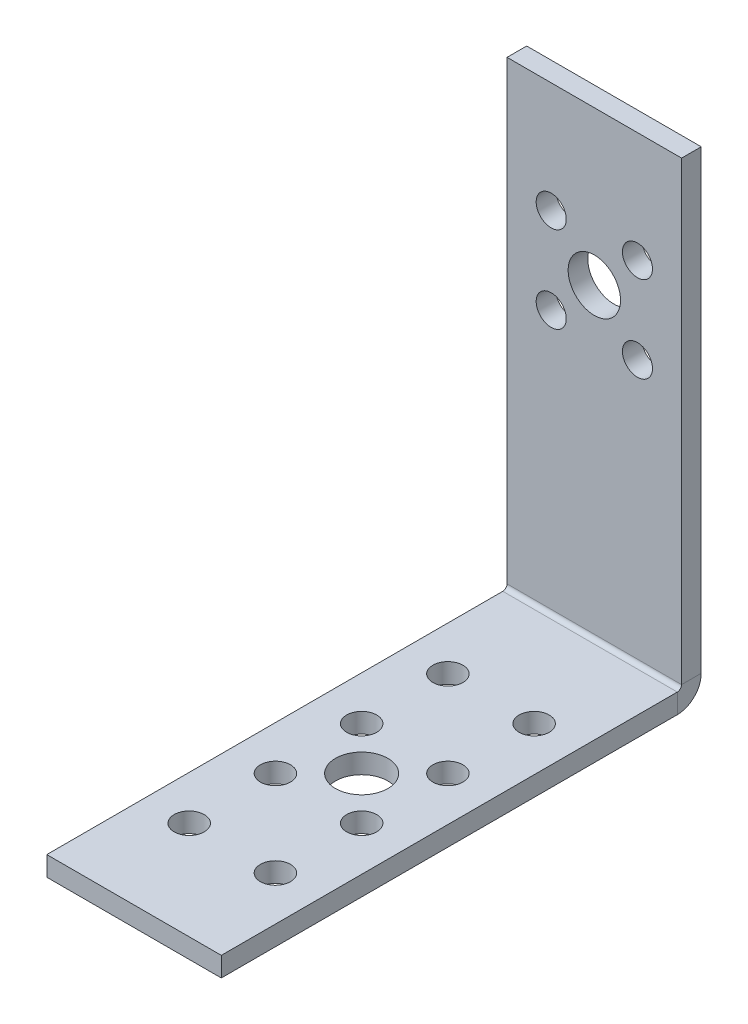
SolidWorks part; units mm, degrees
note: The reader was unsure of these and kept them because the rebuilt part matched: flange length of "Edge-Flange1".
material "6061 Alloy"
ref_plane "Front Plane" through (0, 0, 0) normal (0, 0, 1) x (1, 0, 0)
ref_plane "Top Plane" through (0, 0, 0) normal (0, 1, 0) x (1, 0, 0)
ref_plane "Right Plane" through (0, 0, 0) normal (1, 0, 0) x (0, 0, -1)
sketch "Sketch1" plane through (0, 0, 0) normal (0, 1, 0) x (1, 0, 0)
  line L1 (-10.16, -27.94) -> (10.16, -27.94)
  line L2 (-10.16, -27.94) -> (-10.16, 27.94)
  line L3 (-10.16, 27.94) -> (10.16, 27.94)
  line L4 (10.16, -27.94) -> (10.16, 27.94)
  point P4 (0, -27.94)
  point P5 (-10.16, 0)
  dimension "D1" = 20.32
  dimension "D2" = 55.88
base flange "Base-Flange1" sketch "Sketch1" thickness 2.286 reverse thickness direction no parameters "D1"=0.5
edge flange "Edge-Flange1" sketch "Sketch8" flange angle 90 flange length 55.88 flange position material inside bend radius 0.5 thickness 2.286 relief rectangular parameters "D6"=10
sketch "Sketch8" plane through (0, 0, -27.94) normal (0, 0, -1) x (-1, 0, 0)
  line L0 (-10.16, 0) -> (10.16, 0) construction
  line L1 (-10.16, 0) -> (10.16, 0)
  line L2 (-10.16, 0) -> (-10.16, 53.594)
  line L3 (-10.16, 53.594) -> (10.16, 53.594)
  line L4 (10.16, 53.594) -> (10.16, 0)
bend "EdgeBend1" bend radius 0.5 bend angle 90 parameters "D5"=1
sketch "Sketch9" plane through (0, 0, -27.94) normal (0, 0, -1) x (-1, 0, 0)
  circle A2 centre (0, 35.6955) radius 3.05
  arc A6 (5.0205, 32.4251) -> (5.0205, 28.9251) centre (5.0205, 30.6751) ccw
  arc A7 (5.0205, 28.9251) -> (5.0205, 32.4251) centre (5.0205, 30.6751) ccw
  arc A10 (-5.0205, 42.466) -> (-5.0205, 38.966) centre (-5.0205, 40.716) ccw
  arc A11 (-5.0205, 38.966) -> (-5.0205, 42.466) centre (-5.0205, 40.716) ccw
  arc A14 (-5.0205, 32.4251) -> (-5.0205, 28.9251) centre (-5.0205, 30.6751) ccw
  arc A15 (-5.0205, 28.9251) -> (-5.0205, 32.4251) centre (-5.0205, 30.6751) ccw
  arc A18 (5.0205, 42.466) -> (5.0205, 38.966) centre (5.0205, 40.716) ccw
  arc A19 (5.0205, 38.966) -> (5.0205, 42.466) centre (5.0205, 40.716) ccw
sketch "Sketch10" plane through (0, 0, 0) normal (0, 1, 0) x (1, 0, 0)
  circle A2 centre (-0.01, -1.426) radius 3.05
  circle A4 centre (-5.0305, -16.4874) radius 1.75
  circle A6 centre (-5.0305, 3.5945) radius 1.75
  circle A8 centre (5.0105, 13.6354) radius 1.75
  circle A10 centre (5.0105, -6.4465) radius 1.75
  circle A12 centre (5.0105, -16.4874) radius 1.75
  circle A14 centre (-5.0305, 13.6354) radius 1.75
  circle A16 centre (-5.0305, -6.4465) radius 1.75
  circle A18 centre (5.0105, 3.5945) radius 1.75
extrude "Cut-Extrude1" cut sketch "Sketch9" against normal through all contours A2 | A10 A11 | A14 A15 | A6 A7 | A18 A19 normal cut yes
extrude "Cut-Extrude2" cut sketch "Sketch10" against normal through all normal cut yes
sketch "Bend-Lines1" [suppressed] plane through (0, 0, 0) normal (0, 1, 0) x (1, 0, 0)
sketch "Bounding-Box1" [suppressed] plane through (0, 0, 0) normal (0, 1, 0) x (1, 0, 0)
sheet metal parameters "Sheet-Metal1" thickness 2.286 parameters "D1"=0.5
flat pattern "Flat-Pattern1" [suppressed]
sketch "Bend-Lines2" plane through (0, 0, 0) normal (0, 1, 0) x (1, 0, 0)
sketch3d "Bounding-Box2" [suppressed]
  line L0 (10.16, -21.59, 0) -> (10.16, 21.59, 0) construction
  line L1 (-10.16, -21.59, 0) -> (-10.16, 21.59, 0) construction
  line L2 (10.16, -21.59, 0) -> (-10.16, -21.59, 0) construction
  line L3 (10.16, 21.59, 0) -> (-10.16, 21.59, 0) construction
sheet metal parameters "Sheet-Metal2" thickness 2.286 parameters "D1"=0.5
flat pattern "Flat-Pattern1"
sketch "Bend-Lines2" plane through (0, 0, 0) normal (0, 1, 0) x (1, 0, 0)
  line L0 (10.16, 26.4444) -> (-10.16, 26.4444) construction
  line L1 (10.16, 26.4444) -> (-10.16, 26.4444) construction
sketch3d "Bounding-Box2" [suppressed]
  line L0 (-10.16, -27.94, 0) -> (-10.16, 80.8288, 0) construction
  line L1 (10.16, -27.94, 0) -> (10.16, 80.8288, 0) construction
  line L2 (-10.16, -27.94, 0) -> (10.16, -27.94, 0) construction
  line L3 (-10.16, 80.8288, 0) -> (10.16, 80.8288, 0) construction
bend of the flat pattern "Flatten-<EdgeBend1>1"
sheet metal parameters "Sheet-Metal3" thickness 2.286 parameters "D1"=0.5
flat pattern "Flat-Pattern1"
sketch "Bend-Lines2" plane through (0, 0, 0) normal (0, 1, 0) x (1, 0, 0)
  line L0 (10.16, 26.4444) -> (-10.16, 26.4444) construction
  line L1 (10.16, 26.4444) -> (-10.16, 26.4444) construction
sketch3d "Bounding-Box2" [suppressed]
  line L0 (-10.16, -27.94, 0) -> (-10.16, 80.8288, 0) construction
  line L1 (10.16, -27.94, 0) -> (10.16, 80.8288, 0) construction
  line L2 (-10.16, -27.94, 0) -> (10.16, -27.94, 0) construction
  line L3 (-10.16, 80.8288, 0) -> (10.16, 80.8288, 0) construction
bend of the flat pattern "Flatten-<EdgeBend1>1"
sheet metal parameters "Sheet-Metal4" thickness 2.286 parameters "D1"=0.5
flat pattern "Flat-Pattern1"
sketch "Bend-Lines2" plane through (0, 0, 0) normal (0, 1, 0) x (1, 0, 0)
  line L0 (10.16, 26.4444) -> (-10.16, 26.4444) construction
  line L1 (10.16, 26.4444) -> (-10.16, 26.4444) construction
sketch3d "Bounding-Box2" [suppressed]
  line L0 (-10.16, -27.94, 0) -> (-10.16, 80.8288, 0) construction
  line L1 (10.16, -27.94, 0) -> (10.16, 80.8288, 0) construction
  line L2 (-10.16, -27.94, 0) -> (10.16, -27.94, 0) construction
  line L3 (-10.16, 80.8288, 0) -> (10.16, 80.8288, 0) construction
bend of the flat pattern "Flatten-<EdgeBend1>1"
